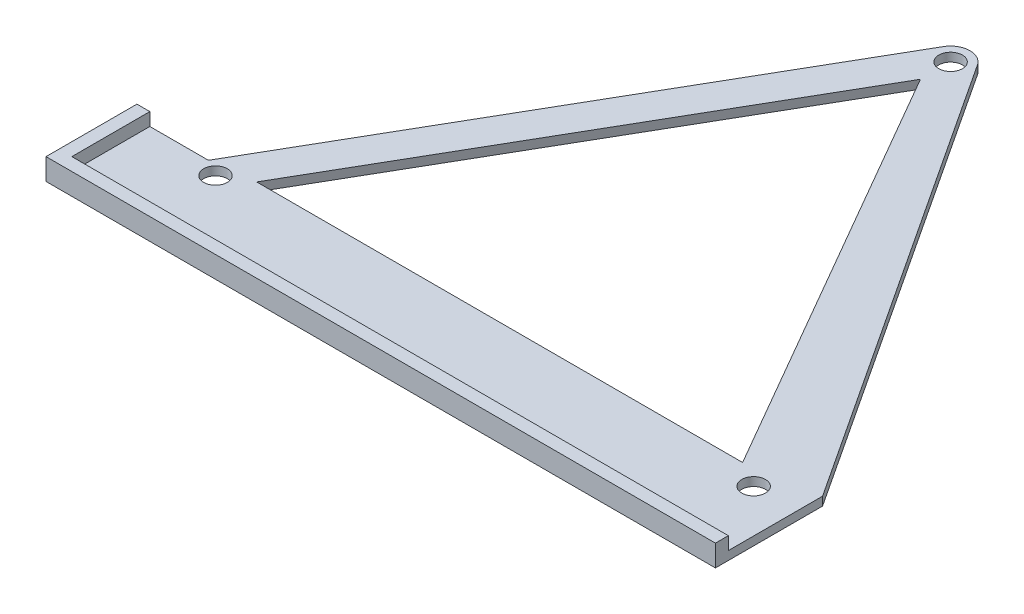
SolidWorks part; units mm, degrees
ref_plane "Front Plane" through (0, 0, 0) normal (0, 0, 1) x (1, 0, 0)
ref_plane "Top Plane" through (0, 0, 0) normal (0, 1, 0) x (1, 0, 0)
ref_plane "Right Plane" through (0, 0, 0) normal (1, 0, 0) x (0, 0, -1)
sketch "Sketch1" plane through (0, 0, 0) normal (0, 1, 0) x (1, 0, 0)
  line L0 (-62.5, -54.1266) -> (0, 54.1266) construction
  line L1 (0, 54.1266) -> (62.5, -54.1266) construction
  line L2 (62.5, -54.1266) -> (-62.5, -54.1266) construction
  line L5 (-3.8971, 56.3766) -> (-66.3971, -51.8766)
  line L6 (72.5, -48.1157) -> (3.8971, 56.3766)
  line L11 (-83, -73) -> (72.5, -73)
  line L17 (0, 54.1266) -> (0, 70) construction
  line L18 (0, -54.1266) -> (0, -70) construction
  line L19 (-83, -73) -> (72.5, -73)
  line L38 (-66.3971, -51.8766) -> (-80, -51.8766)
  line L39 (-80, -51.8766) -> (-83, -51.8766)
  line L40 (-83, -51.8766) -> (-83, -73)
  line L41 (72.5, -70) -> (-80, -70)
  line L42 (-80, -51.8766) -> (-80, -70)
  line L43 (-56.4378, -50.6266) -> (0, 47.1266)
  line L44 (72.5, -73) -> (72.5, -70)
  line L45 (72.5, -48.1157) -> (72.5, -70)
  line L46 (0, 47.1266) -> (56.4378, -50.6266)
  line L47 (56.4378, -50.6266) -> (-56.4378, -50.6266)
  line L49 (-80, -70) -> (80, -70) construction
  line L50 (-80, -70) -> (-80, 70) construction
  line L51 (-80, 70) -> (80, 70) construction
  line L52 (80, -70) -> (80, 70) construction
  line L53 (-80, -70) -> (80, 70) construction
  line L54 (-80, 70) -> (80, -70) construction
  circle A0 centre (0, -18.0422) radius 36.0844 construction
  arc A1 (3.8971, 56.3766) -> (-3.8971, 56.3766) centre (0, 54.1266) ccw
  circle A4 centre (0, 54.1266) radius 2.75
  circle A5 centre (62.5, -54.1266) radius 2.75
  circle A6 centre (-62.5, -54.1266) radius 2.75
  point P10 (0, 0)
  point P24 (0, 0)
  point P31 (0, 70)
  dimension "D2" = 9
  dimension "D5" = 160
  dimension "D7" = 5.5
  dimension "D1" = 125
  dimension "D3" = 120
  dimension "D8" = 140
  dimension "D9" = 7
  dimension "D10" = 7
  dimension "D11" = 7
  dimension "D6" = 10
  dimension "D4" = 3
extrude "Boss-Extrude4" add sketch "Sketch1" along normal blind 2 contours L6 A1 L5 L38 L45 A6 A5 A4 region at (0, 0, -58.4271)
extrude "Boss-Extrude7" add sketch "Sketch1<6>" along normal blind 5 contours L11 L44 L39 L40 region at (-13.2092, 0, 70.3975)
sketch "Sketch1<6>" plane through (0, 0, 0) normal (0, 1, 0) x (1, 0, 0) same geometry as "Sketch1"
